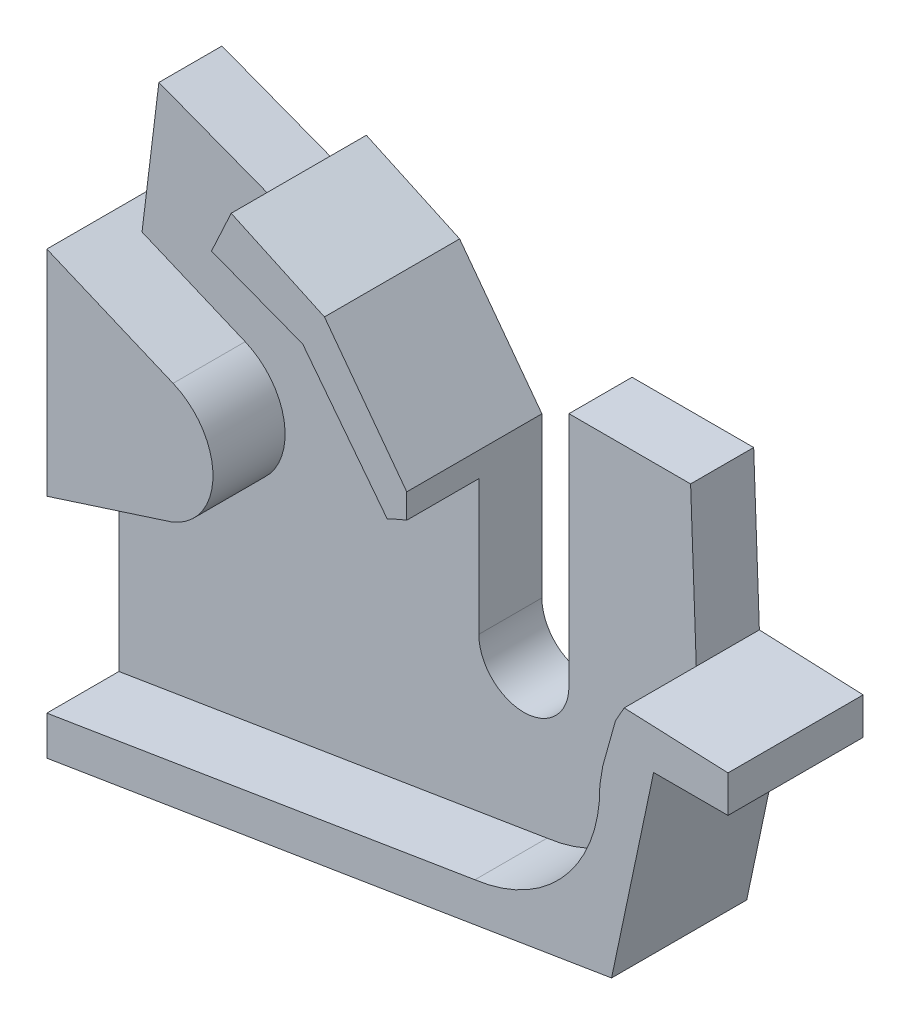
SolidWorks part; units mm, degrees
ref_plane "Front Plane" through (0, 0, 0) normal (0, 0, 1) x (1, 0, 0)
ref_plane "Top Plane" through (0, 0, 0) normal (0, 1, 0) x (1, 0, 0)
ref_plane "Right Plane" through (0, 0, 0) normal (1, 0, 0) x (0, 0, -1)
sketch "Sketch1" plane through (0, 0, 0) normal (0, 0, 1) x (1, 0, 0)
  line L0 (-48.8998, -64.1664) -> (-34.4801, 53.9567) construction
  line L3 (0, 51.4823) -> (78.4652, 51.4823)
  line L4 (78.4652, 0) -> (78.4652, 51.4823)
  line L5 (-0.9054, 14.8469) -> (9.0946, 14.8469)
  line L6 (9.0946, 14.8469) -> (9.0946, -2.1531)
  line L7 (9.0946, -2.1531) -> (-0.9054, -2.1531)
  line L8 (-0.9054, -2.1531) -> (-0.9054, 14.8469)
  line L9 (-12.4514, 28.9758) -> (-0.9054, 14.0572)
  line L10 (-53.6354, 44.7137) -> (-12.4514, 28.9758)
  line L11 (9.0946, 14.8469) -> (9.0946, 29.052)
  line L12 (9.0946, 29.052) -> (22.5946, 29.052)
  line L13 (-62.0404, 32.8316) -> (-26.8328, 18.0034)
  line L14 (-26.8328, 18.0034) -> (-29.6416, 11.3342)
  line L15 (-29.6416, 11.3342) -> (-32.4505, 4.6651)
  line L16 (-70.8332, -9.4959) -> (-26.9614, 4.6123)
  line L17 (-40.8439, 23.9044) -> (-40.8439, 0.148)
  line L18 (-26.9614, 4.6123) -> (-29.6416, 11.3342)
  line L19 (-29.6416, 11.3342) -> (-32.3218, 18.0562)
  line L20 (-74.7301, -26.2138) -> (-1.4754, -14.2813)
  line L21 (-1.4754, -14.2813) -> (7.6299, -12.7982)
  line L22 (23.2246, 11.8381) -> (22.2572, 10.123)
  line L23 (23.2246, 11.8381) -> (34.7443, 11.3546)
  line L24 (-0.9054, 14.8469) -> (-0.9054, 20.5391)
  line L25 (-0.9054, 20.5391) -> (-7.2539, 29.052)
  line L26 (-7.2539, 29.052) -> (-10.0368, 32.7838)
  line L27 (-10.0368, 32.7838) -> (-20.3866, 37.57)
  line L28 (-20.3866, 37.57) -> (-22.5724, 32.8434)
  line L29 (-70.8332, -25.579) -> (-70.1459, -29.7983)
  line L30 (-70.1459, -29.7983) -> (21.8227, -14.8175)
  line L31 (21.8227, -14.8175) -> (26.4898, 7.2668)
  line L32 (26.4898, 7.2668) -> (34.7443, 7.2668)
  line L33 (34.7443, 7.2668) -> (34.7443, 11.3546)
  line L35 (-70.8332, -25.579) -> (-70.8332, -9.4959)
  line L36 (22.5946, 29.052) -> (23.2246, 11.8381)
  line L37 (-40.8439, 0.148) -> (-40.8439, -25.0253)
  line L38 (-40.8439, 23.9044) -> (-40.8439, 39.8257)
  line L39 (22.2572, 10.123) -> (21.4546, 7.2463)
  line L40 (21.4546, 7.2463) -> (20.8501, 5.08)
  line L41 (20.8501, 5.08) -> (20.5233, 3.0772)
  circle A0 centre (4.0946, 2.8469) radius 5
  circle A1 centre (4.0946, 9.8469) radius 5
  circle A2 centre (-29.6416, 11.3342) radius 7.2365
  circle A3 centre (4.5867, 2.8469) radius 15.9383
  point P47 (0, 0)
  point P52 (-53.6354, 44.7137)
  point P53 (-12.3555, 29.052)
  point P54 (-12.4514, 28.9758)
  point P55 (-70.8332, -9.4959)
  point P56 (-26.9473, 4.6632)
  point P57 (-40.8439, 23.6566)
  point P58 (-26.8328, 18.0562)
  dimension "D4" = 13.5
  dimension "D1" = 119
  dimension "D2" = 10
  dimension "D3" = 17
extrude "Boss-Extrude2" add sketch "Sketch1" along normal blind 7 contours L0 L13 A2 L16 L37 L20 L21 A3 L9 L10 | L0 L17 L16 A2 L13 | A3 L24 L25 L26 L27 L28 L10 L9 | A3 L11 L6 L7 L8 L9 L21 | L24 A3 L9 L8 | A3 L41 L40 L39 L22 L36 L12 L11 | A3 L21 L20 L37 L30 L31 L32 L33 L23 L22 L39 L40 L41 | L21 A3 | A0 L8 L7 | A0 L7 L6 | A2 region at (-40.003, -22.8597, 0) region at (-22.7315, 5.6576, 0) region at (-39.2976, 12.2929, 0) region at (-10.1411, -1.9589, 0) region at (7.1484, -12.8796, 0) region at (-1.6279, 16.252, 0) region at (-10.965, 28.4175, 0) region at (16.9275, 20.4665, 0) region at (0.2115, -1.0363, 0) region at (7.9778, -1.0363, 0)
extrude "Boss-Extrude3" add sketch "Sketch1<7>" along normal blind 15 contours L0 L16 A2 L13 | L19 A2 L15 | L16 L0 L13 L17 | L18 A2 L14 | L15 A2 L18 | L14 A2 L19 | A3 L24 L25 L26 L27 L28 L10 | A3 L21 L20 L37 L30 L31 L32 L33 L23 region at (-40.003, -22.8597, 0) region at (-39.9895, 16.1849, 0) region at (-39.2976, 12.2929, 0) region at (-29.688, 6.632, 0) region at (-25.8646, 11.298, 0) region at (-29.5965, 16.0376, 0) region at (-33.4187, 11.3705, 0) region at (-10.965, 28.4175, 0)
sketch "Sketch1<7>" plane through (0, 0, 0) normal (0, 0, 1) x (1, 0, 0) same geometry as "Sketch1"
